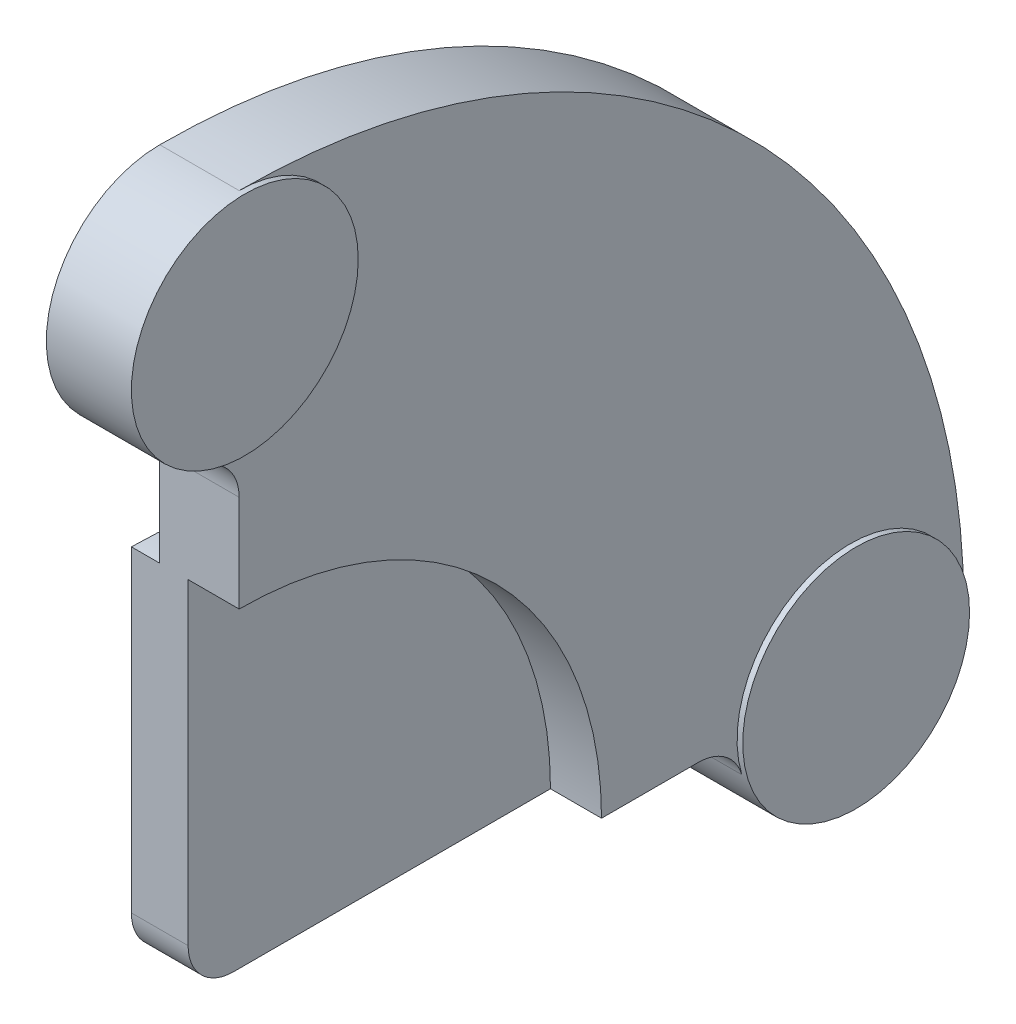
SolidWorks part; units mm, degrees
ref_plane "Alzado" through (0, 0, 0) normal (0, 0, 1) x (1, 0, 0)
ref_plane "Planta" through (0, 0, 0) normal (0, 1, 0) x (1, 0, 0)
ref_plane "Vista lateral" through (0, 0, 0) normal (1, 0, 0) x (0, 0, -1)
sketch "Croquis2" plane through (0, 0, 0) normal (1, 0, 0) x (0, 0, -1)
  line L0 (0, 43.9) -> (0, 0)
  line L1 (0, 0) -> (43.9, 0)
  arc A0 (63.9, 0) -> (0, 63.9) centre (0, 0) ccw
  circle A1 centre (0, 53.9) radius 10
  circle A2 centre (53.9, 0) radius 10
  arc A3 (31.95, 0) -> (0, 31.95) centre (0, 0) ccw
  dimension "D1" = 127.8
  dimension "D2" = 20
  dimension "D3" = 20
  dimension "D4" = 63.9
  dimension "D5" = 53.9
  dimension "D6" = 20
extrude "Saliente-Extruir1" add sketch "Croquis2" along normal mid plane 5 contours L1 A3 L0 region at (0, 13.56, -13.56)
extrude "Saliente-Extruir2" add sketch "Croquis2<3>" along normal blind 7 contours A3 L1 A2 A0 A1 L0 region at (0, 32.0258, -32.0258)
sketch "Croquis2<3>" plane through (0, 0, 0) normal (1, 0, 0) x (0, 0, -1) same geometry as "Croquis2"
extrude "Saliente-Extruir3" add sketch "Croquis2<4>" along normal blind 7.5 contours A1 | A2 region at (0, 53.9, 0) region at (0, 0, -53.9)
sketch "Croquis2<4>" plane through (0, 0, 0) normal (1, 0, 0) x (0, 0, -1) same geometry as "Croquis2"
fillet "Redondeo1" radius 4 1 edges at (0, 0, 0)
fillet "Redondeo2" radius 4 2 edges at (3.5, 0, -43.9) (3.5, 43.9, 0)
